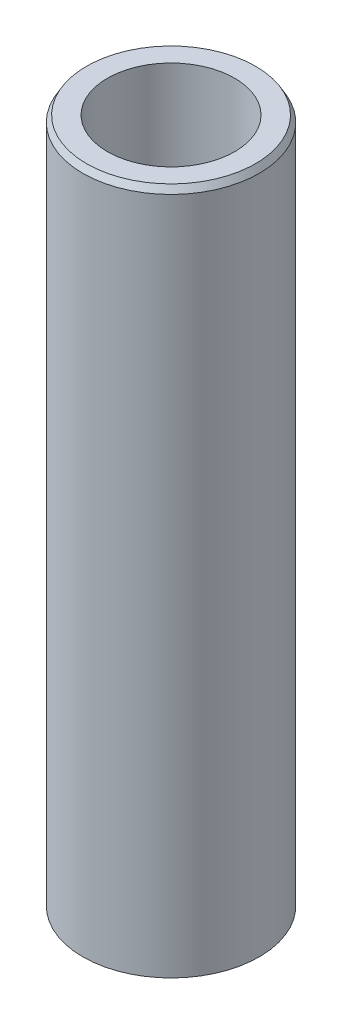
SolidWorks part; units mm, degrees
ref_plane "Front Plane" through (0, 0, 0) normal (0, 0, 1) x (1, 0, 0)
ref_plane "Top Plane" through (0, 0, 0) normal (0, 1, 0) x (1, 0, 0)
ref_plane "Right Plane" through (0, 0, 0) normal (1, 0, 0) x (0, 0, -1)
sketch "Sketch1" plane through (0, 0, 0) normal (0, 1, 0) x (1, 0, 0)
  circle A0 centre (0, 0) radius 37.5
  dimension "SHAFT_OD" = 75
extrude "Boss-Extrude1" add sketch "Sketch1" along normal blind 292.7685
sketch "Sketch2" plane through (0, 0, 0) normal (0, 1, 0) x (1, 0, 0)
  circle A0 centre (0, 0) radius 27.0588
  dimension "BORE_D" = 54.1177
extrude "Cut-Extrude1" cut sketch "Sketch2" along normal through all
chamfer "Chamfer1" distance 2.7531 angle 30 2 edges at (0, 292.7685, 37.5) (0, 0, 37.5) first distance on face at (0, 292.7685, 37.5) first distance on face at (0, 0, 27.0588)
